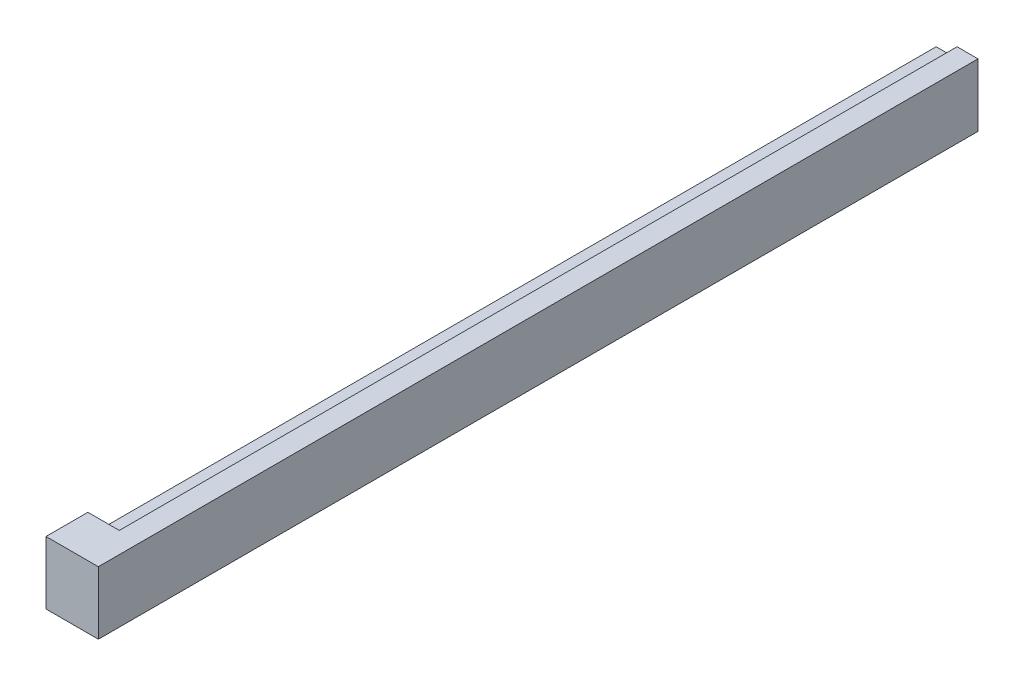
SolidWorks part; units mm, degrees
ref_plane "Front Plane" through (0, 0, 0) normal (0, 0, 1) x (1, 0, 0)
ref_plane "Top Plane" through (0, 0, 0) normal (0, 1, 0) x (1, 0, 0)
ref_plane "Right Plane" through (0, 0, 0) normal (1, 0, 0) x (0, 0, -1)
other "Center of Mass"
sketch "Sketch1" plane through (0, 0, 0) normal (0, 0, 1) x (1, 0, 0)
  line L0 (0, 0) -> (0, 25)
  line L1 (0, 25) -> (25, 25)
  line L2 (25, 25) -> (25, 50)
  line L3 (25, 50) -> (50, 50)
  line L4 (50, 50) -> (50, 25)
  line L5 (50, 25) -> (75, 25)
  line L6 (75, 25) -> (75, 75)
  line L7 (75, 75) -> (125, 75)
  line L8 (125, 75) -> (125, -75)
  line L9 (125, -75) -> (75, -75)
  line L10 (75, -75) -> (75, -25)
  line L11 (75, -25) -> (50, -25)
  line L12 (50, -25) -> (50, -50)
  line L13 (50, -50) -> (25, -50)
  line L14 (25, -50) -> (25, -25)
  line L15 (25, -25) -> (0, -25)
  line L16 (0, -25) -> (0, 0)
  dimension "D1" = 25
  dimension "D2" = 25
  dimension "D3" = 25
  dimension "D4" = 25
  dimension "D5" = 25
  dimension "D6" = 50
  dimension "D7" = 50
  dimension "D8" = 25
  dimension "D9" = 25
  dimension "D10" = 50
  dimension "D11" = 25
  dimension "D12" = 25
  dimension "D13" = 25
  dimension "D14" = 25
  dimension "D15" = 25
extrude "Boss-Extrude1" add sketch "Sketch1" along normal mid plane 2000
sketch "Sketch2" plane through (0, 0, 1000) normal (0, 0, 1) x (1, 0, 0)
  line L1 (0, 75) -> (125, 75)
  line L2 (0, 75) -> (0, -75)
  line L3 (0, -75) -> (125, -75)
  line L4 (125, 75) -> (125, -75)
  line L5 (0, 75) -> (125, -75) construction
  line L6 (0, -75) -> (125, 75) construction
  point P0 (62.5, 0)
  dimension "D1" = 150
  dimension "D2" = 125
extrude "Boss-Extrude2" add sketch "Sketch2" along normal blind 100
sketch "Sketch3" plane through (0, 0, -1000) normal (0, 0, -1) x (-1, 0, 0)
  line L0 (68.75, 0) -> (-68.75, 0) construction
  circle A0 centre (-100, 50) radius 10
  circle A1 centre (-100, -50) radius 10
  dimension "D1" = 100
  dimension "D3" = 20
  dimension "D2" = 50
extrude "Cut-Extrude1" cut sketch "Sketch3" against normal blind 10
ref_plane "Plane1" through (0, 0, 0) normal (0, 1, 0) x (1, 0, 0)
ref_plane "Plane2" through (37.5, 0, 0) normal (-1, 0, 0) x (0, 0, 1)
ref_axis "Link_3_Axis" through (37.5, 0, -1100) along (0, 0, 1)
